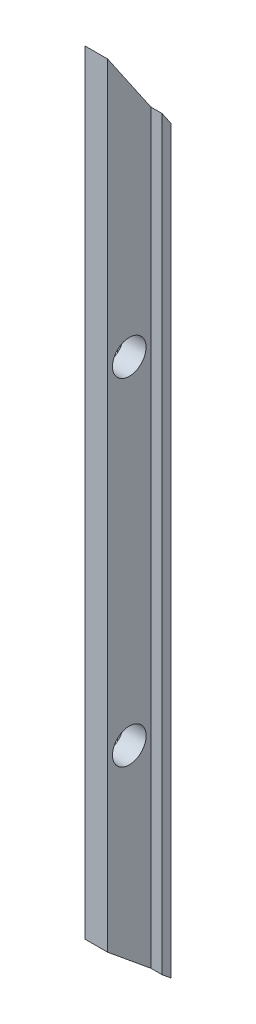
SolidWorks part; units mm, degrees
ref_plane "Front Plane" through (0, 0, 0) normal (0, 0, 1) x (1, 0, 0)
ref_plane "Top Plane" through (0, 0, 0) normal (0, 1, 0) x (1, 0, 0)
ref_plane "Right Plane" through (0, 0, 0) normal (1, 0, 0) x (0, 0, -1)
sketch "Sketch1" plane through (0, 0, 0) normal (0, 0, 1) x (1, 0, 0)
  line L1 (-2, -33) -> (2, -33)
  line L2 (-2, -33) -> (-2, 33)
  line L3 (-2, 33) -> (2, 33)
  line L4 (2, -33) -> (2, 33)
  line L5 (-2, -33) -> (2, 33) construction
  line L6 (-2, 33) -> (2, -33) construction
  point P0 (0, 0)
  dimension "D1" = 4
  dimension "D2" = 66
sketch "Sketch2" plane through (0, 0, 0) normal (1, 0, 0) x (0, 0, -1)
  line L0 (0, 33) -> (-28233.9475, 41298.5329) construction
  line L2 (0, 33) -> (0, -33) construction
  dimension "D1" = 34.38
sketch "Sketch3" plane through (0, 0, 0) normal (1, 0, 0) x (0, 0, -1)
  line L0 (0, -33) -> (38636.6787, -31769.5257) construction
  line L2 (0, -33) -> (0, 33) construction
  dimension "D1" = 50.6
extrude "Boss-Extrude1" add sketch "Sketch1" along direction (0, -0.6347, -0.7727) on the side of the normal blind 1
extrude "Boss-Extrude2" add sketch "Sketch1<2>" along direction (0, 0.8253, 0.5647) on the side of the normal up to surface (0.7727 mm away) up to face at (0, 0.6347, 0.7727)
sketch "Sketch1<2>" plane through (0, 0, 0) normal (0, 0, 1) x (1, 0, 0) same geometry as "Sketch1"
sketch "Sketch4" plane through (0, 0, 0.7727) normal (0, 0, 1) x (1, 0, 0)
  line L0 (-2, -32.3653) -> (2, -32.3653) construction
  line L1 (-1, -32.3653) -> (1, -32.3653)
  line L2 (-1, -32.3653) -> (-1, 34.1294)
  line L3 (-1, 34.1294) -> (1, 34.1294)
  line L4 (1, -32.3653) -> (1, 34.1294)
  line L5 (-1, -32.3653) -> (1, 34.1294) construction
  line L6 (-1, 34.1294) -> (1, -32.3653) construction
  line L7 (-2, 34.1294) -> (2, 34.1294) construction
  line L8 (0, -165029.1317) -> (0, 206360.6647) construction
  point P4 (0, 0.8821)
  point P9 (0, 34.1294)
  dimension "D1" = 2
extrude "Boss-Extrude3" add sketch "Sketch4" along direction (0, -0.6347, -0.7727) on the side of the normal blind 5
extrude "Boss-Extrude4" add sketch "Sketch4<2>" along direction (0, 0.8253, 0.5647) on the side of the normal up to surface (3.8637 mm away) up to face at (0, 4.0557, 4.6364)
sketch "Sketch4<2>" plane through (0, 0, 0.7727) normal (0, 0, 1) x (1, 0, 0) same geometry as "Sketch4"
hole_wizard "Ø3.0mm Dowel Hole1" positions "Sketch6" profile "Sketch8" hole size "Ø3.0" standard "ANSI Metric" end condition through all
sketch "Sketch6" plane through (-1, 0, 0) normal (-1, 0, 0) x (0, 0, 1)
  line L3 (2.7046, -14.1916) -> (4.6364, -14.1916) construction
  line L4 (4.6364, 39.7764) -> (4.6364, -29.1916) construction
  line L6 (2.7046, -14.1916) -> (0.7727, -14.1916) construction
  line L7 (0.7727, 34.1294) -> (0.7727, -32.3653) construction
  point P0 (2.7046, -14.1916)
  point P2 (2.7046, 15.8084)
  dimension "D1" = 15
  dimension "D2" = 45
sketch "Sketch8" plane through (-1, -14.1916, 2.7046) normal (0, 1, 0) x (0, 0, 1)
  line L0 (0, 0) -> (0, 3)
  line L1 (0, 3) -> (1.5, 3)
  line L2 (1.5, 3) -> (1.5, 0)
  line L5 (1.5, 0) -> (0, 0)
  line L11 (0, -6.35) -> (0, 107.95) construction
  dimension "Thru Hole Dia." = 3
  dimension "Thru Hole Depth" = 3
